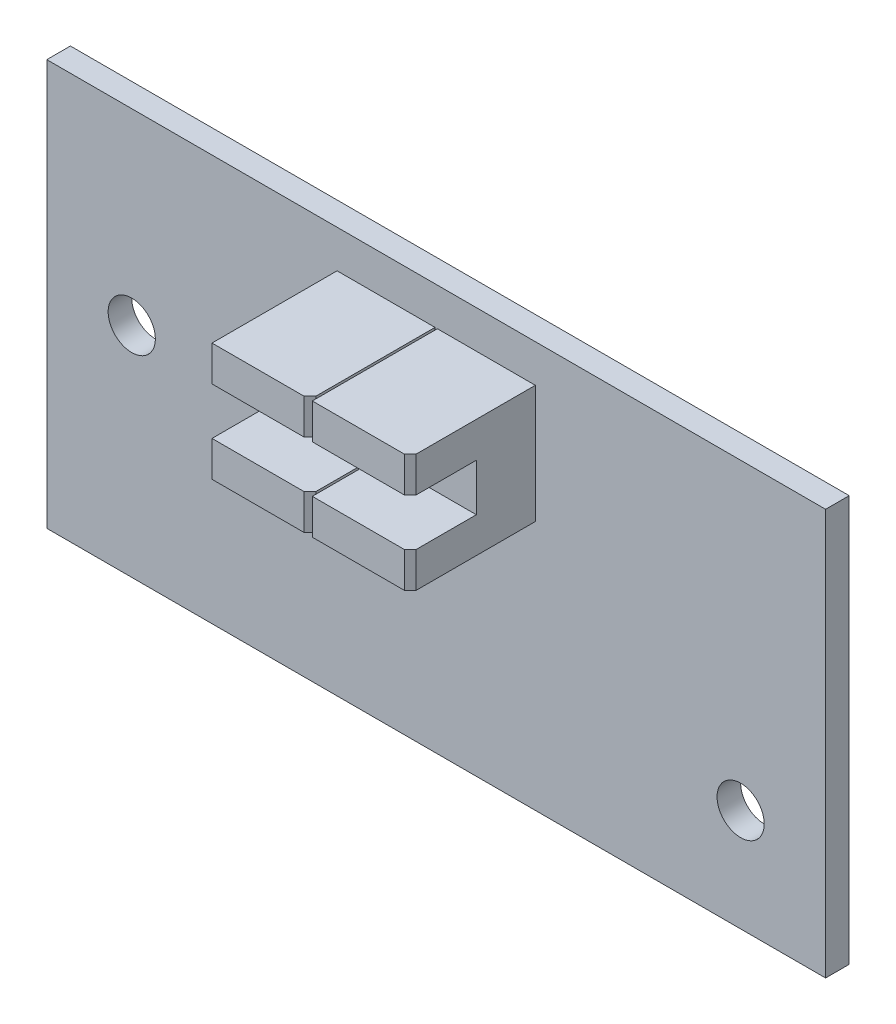
SolidWorks part; units mm, degrees
ref_plane "Alzado" through (0, 0, 0) normal (0, 0, 1) x (1, 0, 0)
ref_plane "Planta" through (0, 0, 0) normal (0, 1, 0) x (1, 0, 0)
ref_plane "Vista lateral" through (0, 0, 0) normal (1, 0, 0) x (0, 0, -1)
sketch "Croquis1" plane through (0, 0, 0) normal (0, 0, 1) x (1, 0, 0)
  line L1 (-16.5, -8.6) -> (16.5, -8.6)
  line L2 (-16.5, -8.6) -> (-16.5, 8.6)
  line L3 (-16.5, 8.6) -> (16.5, 8.6)
  line L4 (16.5, -8.6) -> (16.5, 8.6)
  line L5 (-16.5, -8.6) -> (16.5, 8.6) construction
  line L6 (-16.5, 8.6) -> (16.5, -8.6) construction
  circle A0 centre (-12.9, 0.65) radius 1
  circle A1 centre (12.9, -4.25) radius 1
  point P0 (0, 0)
  dimension "D3" = 2
  dimension "D1" = 33
  dimension "D2" = 17.2
  dimension "D4" = 7.95
  dimension "D5" = 4.35
  dimension "D6" = 3.6
  dimension "D7" = 3.6
extrude "Saliente-Extruir1" add sketch "Croquis1" along normal blind 1
sketch "Croquis2" plane through (0, 0, 1) normal (0, 0, 1) x (1, 0, 0)
  line L0 (16.5, 8.6) -> (-16.5, 8.6) construction
  line L1 (-4.2, 7) -> (4.2, 7)
  line L2 (-4.2, 7) -> (-4.2, 2)
  line L3 (-4.2, 2) -> (4.2, 2)
  line L4 (4.2, 7) -> (4.2, 2)
  line L5 (-4.2, 7) -> (4.2, 2) construction
  line L6 (-4.2, 2) -> (4.2, 7) construction
  line L12 (-4.2, 2) -> (4.2, 2)
  line L13 (-4.2, 2) -> (-4.2, 3.5)
  line L14 (-4.2, 3.5) -> (4.2, 3.5)
  line L15 (4.2, 2) -> (4.2, 3.5)
  line L16 (4.2, 7) -> (-4.2, 7)
  line L17 (4.2, 7) -> (4.2, 5.5)
  line L18 (4.2, 5.5) -> (-4.2, 5.5)
  line L19 (-4.2, 7) -> (-4.2, 5.5)
  point P0 (0, 4.5)
  dimension "D1" = 5
  dimension "D2" = 1.6
  dimension "D3" = 8.4
  dimension "D4" = 2
  dimension "D5" = 1.5
extrude "Saliente-Extruir2" add sketch "Croquis2" along normal blind 2.5 contours L2 L3 L4 L1
extrude "Saliente-Extruir3" add sketch "Croquis2<5>" along normal blind 5.3 contours L14 L2 L3 L4 | L18 L4 L1 L2 region at (0, 6.25, 1) region at (0, 2.75, 1)
sketch "Croquis2<5>" plane through (0, 0, 1) normal (0, 0, 1) x (1, 0, 0) same geometry as "Croquis2"
sketch "Croquis3" plane through (0, 0, 6.3) normal (0, 0, 1) x (1, 0, 0)
  line L0 (-4.2, 7) -> (4.2, 7) construction
  line L1 (-0.05, 7) -> (0.05, 7)
  line L2 (-0.05, 7) -> (-0.05, 2)
  line L3 (-0.05, 2) -> (0.05, 2)
  line L4 (0.05, 7) -> (0.05, 2)
  line L5 (-4.2, 2) -> (4.2, 2) construction
  point P8 (0, 7)
  dimension "D1" = 0.1
extrude "Cortar-Extruir1" cut sketch "Croquis3" against normal up to surface (5.3 mm away) up to face at (0, 4.5, 1)
chamfer "Chaflán1" distance 0.25 angle 45 4 edges at (4.2, 2.75, 6.3) (4.2, 6.25, 6.3) (-0.05, 2.75, 6.3) (-0.05, 6.25, 6.3)
equation "\"D7@Croquis1\"=\"D6@Croquis1\""
